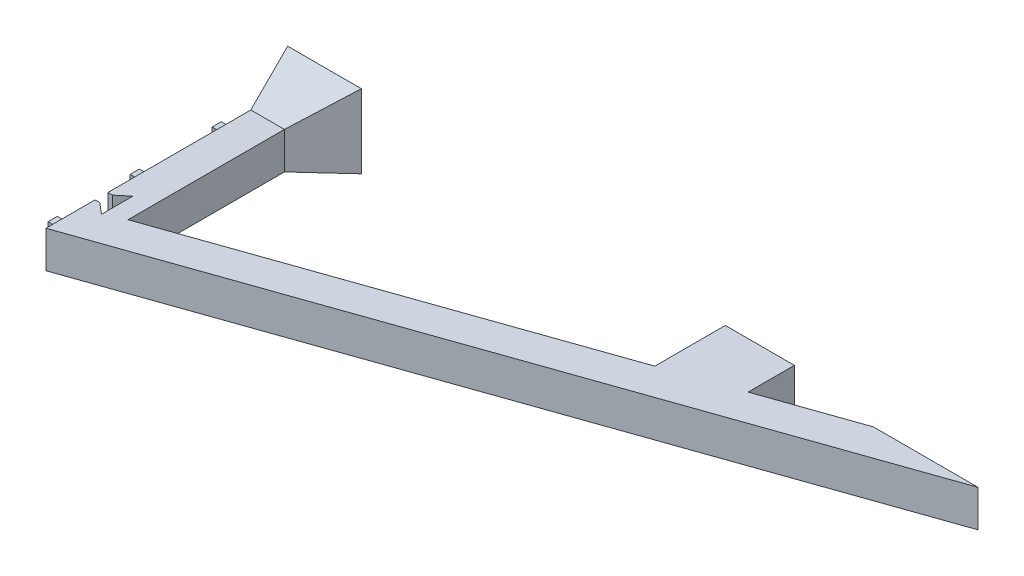
SolidWorks part; units mm, degrees
ref_plane "Přední rovina" through (0, 0, 0) normal (0, 0, 1) x (1, 0, 0)
ref_plane "Horní rovina" through (0, 0, 0) normal (0, 1, 0) x (1, 0, 0)
ref_plane "Pravá rovina" through (0, 0, 0) normal (1, 0, 0) x (0, 0, -1)
sketch "Skica1" plane through (0, 0, 0) normal (0, 1, 0) x (1, 0, 0)
  line L0 (0, 0) -> (0, -55.45)
  line L1 (0, -55.45) -> (149.85, -3)
  line L2 (149.85, -3) -> (127.1478, -3)
  line L3 (127.1478, -3) -> (107, -10.0521)
  line L4 (107, -10.0521) -> (107, 0)
  line L5 (107, 0) -> (92, 0)
  line L6 (92, 0) -> (92, -15.3023)
  line L7 (92, -15.3023) -> (7.3, -44.9487)
  line L8 (7.3, -44.9487) -> (7.3, 0)
  line L9 (7.3, 0) -> (0, 0)
  point P3 (92, -7.6512)
  dimension "D1" = 55.45
  dimension "D2" = 7.3
  dimension "D3" = 15
  dimension "D4" = 3
  dimension "D5" = 7.5
  dimension "D6" = 7.5
  dimension "D7" = 84.7
  dimension "D8" = 149.85
extrude "Přidat vysunutím1" add sketch "Skica1" along normal blind 8
sketch "Skica2" plane through (0, 8, 0) normal (0, 1, 0) x (1, 0, 0)
  line L6 (0, -42) -> (1, -42)
  line L7 (0, 0) -> (0, -55.45) construction
  line L8 (1, -42) -> (3.4, -40)
  line L9 (3.4, -40) -> (3.4, -46.8)
  line L10 (3.4, -46.8) -> (1, -44.8)
  line L11 (1, -44.8) -> (0, -44.8)
  line L12 (0, -44.8) -> (0, -42)
  line L13 (7.3, 0) -> (0, 0) construction
  dimension "D1" = 1
  dimension "D2" = 1
  dimension "D3" = 3.4
  dimension "6,8" = 6.8
  dimension "2,8" = 2.8
  dimension "D4" = 2
  dimension "4" = 40
extrude "Odebrat vysunutím1" cut sketch "Skica2" against normal blind 4.4
sketch "Skica3" plane through (0, 0, 0) normal (-1, 0, 0) x (0, 0, 1)
  line L1 (13.4, 5) -> (15.4, 5)
  line L2 (13.4, 5) -> (13.4, 3)
  line L3 (13.4, 3) -> (15.4, 3)
  line L4 (15.4, 5) -> (15.4, 3)
  line L5 (31.2, 5) -> (33.2, 5)
  line L6 (31.2, 5) -> (31.2, 3)
  line L7 (31.2, 3) -> (33.2, 3)
  line L8 (33.2, 5) -> (33.2, 3)
  line L9 (49, 5) -> (51, 5)
  line L10 (49, 5) -> (49, 3)
  line L11 (49, 3) -> (51, 3)
  line L12 (51, 5) -> (51, 3)
  line L13 (0, 8) -> (0, 0) construction
  line L14 (0, 8) -> (42, 8) construction
  line L15 (44.8, 8) -> (55.45, 8) construction
  dimension "D1" = 2
  dimension "D2" = 2
  dimension "D3" = 2
  dimension "D4" = 2
  dimension "D5" = 2
  dimension "D6" = 2
  dimension "D7" = 13.4
  dimension "D8" = 3
  dimension "D9" = 3
  dimension "D10" = 3
  dimension "D11" = 15.8
  dimension "D12" = 15.8
extrude "Přidat vysunutím2" add sketch "Skica3" along normal blind 4
sketch "Skica5" plane through (0, 8, 0) normal (0, 1, 0) x (1, 0, 0)
  line L0 (0, 0) -> (0, -42) construction
  line L5 (0, -3) -> (16, -3)
  line L6 (0, -3) -> (0, -11)
  line L7 (0, -11) -> (16, -11)
  line L8 (16, -3) -> (16, -11)
  line L9 (7.3, 0) -> (0, 0) construction
  dimension "D1" = 8
  dimension "D2" = 3
  dimension "D3" = 16
extrude "Přidat vysunutím4" add sketch "Skica5" against normal blind 16 from offset 8
sketch "Skica6" plane through (0, 0, 0) normal (-1, 0, 0) x (0, 0, 1)
  line L3 (3, 16) -> (11, 16)
  line L4 (11, 16) -> (11, 8)
  line L5 (11, 8) -> (3, 16)
extrude "Odebrat vysunutím2" cut sketch "Skica6" against normal through all
sketch "Skica7" plane through (0, 0, 0) normal (0, -1, 0) x (1, 0, 0)
  line L3 (7.3, 11) -> (16, 11)
  line L4 (16, 11) -> (16, 3)
  line L5 (16, 3) -> (7.3, 11)
extrude "Odebrat vysunutím3" cut sketch "Skica7" against normal through all
